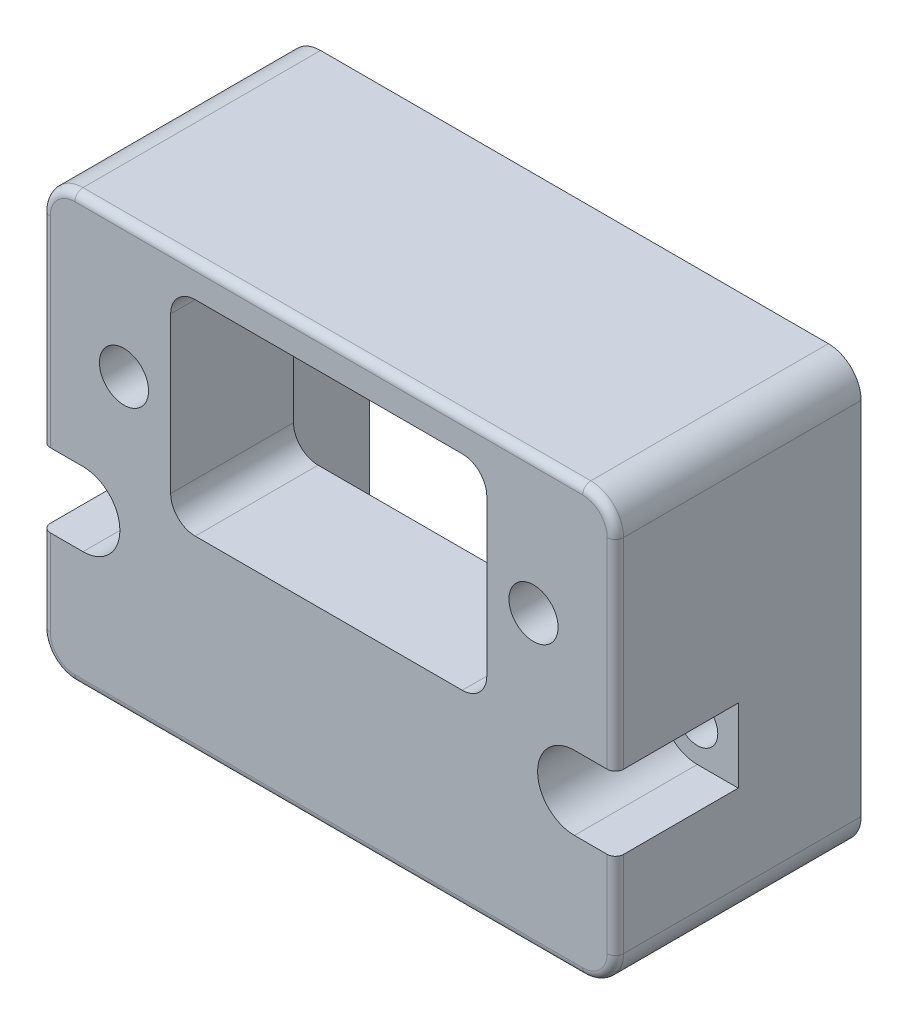
SolidWorks part; units mm, degrees
ref_plane "Спереди" through (0, 0, 0) normal (0, 0, 1) x (1, 0, 0)
ref_plane "Сверху" through (0, 0, 0) normal (0, 1, 0) x (1, 0, 0)
ref_plane "Справа" through (0, 0, 0) normal (1, 0, 0) x (0, 0, -1)
sketch "Эскиз1" plane through (0, 0, 0) normal (0, 0, 1) x (1, 0, 0)
  line L0 (17.5, 66.1888) -> (17.5, -23.9773) construction
  line L1 (0, 0) -> (35, 0)
  line L2 (0, 0) -> (0, 26)
  line L3 (0, 26) -> (35, 26)
  line L4 (35, 0) -> (35, 26)
  line L5 (0, 9.5) -> (100.0729, 9.5) construction
  circle A0 centre (2.5, 9.5) radius 1.25
  circle A1 centre (32.5, 9.5) radius 1.25
  dimension "D4" = 2.5
  dimension "D5" = 30
  dimension "D1" = 16.5
  dimension "D2" = 35
  dimension "D3" = 26
extrude "Вытянуть1" add sketch "Эскиз1" along normal blind 15
sketch "Эскиз2" plane through (0, 0, 0) normal (0, 0, -1) x (-1, 0, 0)
  line L0 (-17.5, 26) -> (-17.5, -0.9688) construction
  line L1 (-35, 26) -> (0, 26) construction
  line L2 (-35, 0) -> (-35, 26) construction
  line L3 (0, 26) -> (0, 0) construction
  line L4 (0, 0) -> (-35, 0) construction
  line L5 (-30, 2) -> (-5, 2)
  line L6 (-30, 2) -> (-30, 16.25)
  line L7 (-30, 24) -> (-5, 24)
  line L8 (-5, 2) -> (-5, 16.25)
  line L9 (-37.7202, 17.75) -> (3.5778, 17.75) construction
  line L10 (-30, 19.25) -> (-30, 24)
  line L11 (-5, 19.25) -> (-5, 24)
  arc A0 (-30, 19.25) -> (-30, 16.25) centre (-30, 17.75) ccw
  arc A1 (-5, 16.25) -> (-5, 19.25) centre (-5, 17.75) ccw
  dimension "D6" = 1.5
  dimension "D7" = 1.5
  dimension "D1" = 25
  dimension "D2" = 12.5
  dimension "D3" = 2
  dimension "D4" = 22
  dimension "D5" = 6.25
extrude "Вырез-Вытянуть1" cut sketch "Эскиз2" against normal blind 7.5
fillet "Скругление1" radius 1.5
fillet "Скругление2" radius 0.5
sketch "Эскиз8" plane through (0, 0, 15) normal (0, 0, 1) x (1, 0, 0)
  line L0 (-1.0855, 17.75) -> (36.4369, 17.75) construction
  line L1 (0, 26) -> (35, 26) construction
  line L2 (17.5, 28.989) -> (17.5, 9.7378) construction
  line L3 (0, 0) -> (0, 26) construction
  line L4 (35, 26) -> (35, 0) construction
  line L6 (9.35, 11.5) -> (25.65, 11.5)
  line L7 (7.85, 13) -> (7.85, 22.5)
  line L8 (9.35, 24) -> (25.65, 24)
  line L9 (27.15, 13) -> (27.15, 22.5)
  circle A0 centre (5, 17.75) radius 1.5
  circle A1 centre (30, 17.75) radius 1.5
  arc A2 (25.65, 24) -> (27.15, 22.5) centre (25.65, 22.5) cw
  arc A3 (25.65, 11.5) -> (27.15, 13) centre (25.65, 13) ccw
  arc A4 (9.35, 11.5) -> (7.85, 13) centre (9.35, 13) cw
  arc A5 (7.85, 22.5) -> (9.35, 24) centre (9.35, 22.5) cw
  point P20 (27.15, 24)
  point P23 (27.15, 11.5)
  dimension "D2" = 25
  dimension "D3" = 3
  dimension "D6" = 1.5
  dimension "D1" = 8.25
  dimension "D4" = 12.5
  dimension "D5" = 19.3
extrude "Вырез-Вытянуть5" cut sketch "Эскиз8" against normal blind 10
sketch "Эскиз9" plane through (0, 0, 15) normal (0, 0, 1) x (1, 0, 0)
  line L1 (2.5, 7.25) -> (-1.2807, 7.25)
  line L3 (2.5, 11.75) -> (-1.2807, 11.75)
  line L4 (-1.2807, 7.25) -> (-1.2807, 11.75)
  line L5 (32.5, 7.25) -> (36.2807, 7.25)
  line L7 (32.5, 11.75) -> (36.2807, 11.75)
  line L8 (36.2807, 7.25) -> (36.2807, 11.75)
  arc A0 (2.5, 7.25) -> (2.5, 11.75) centre (2.5, 9.5) ccw
  arc A1 (32.5, 11.75) -> (32.5, 7.25) centre (32.5, 9.5) ccw
  dimension "D1" = 4.5
extrude "Вырез-Вытянуть6" cut sketch "Эскиз9" against normal blind 7.5
fillet "Скругление3" radius 2
sketch "Эскиз10" plane through (0, 0, 0) normal (0, 0, -1) x (-1, 0, 0)
  circle A0 centre (-5, 17.75) radius 4
  circle A1 centre (-30, 17.75) radius 4
  arc A2 (-30, 16.25) -> (-30, 19.25) centre (-30, 17.75) ccw construction
  arc A3 (-5, 19.25) -> (-5, 16.25) centre (-5, 17.75) ccw construction
  dimension "D1" = 8
extrude "Вырез-Вытянуть7" cut sketch "Эскиз10" against normal up to surface (7.5 mm away)
